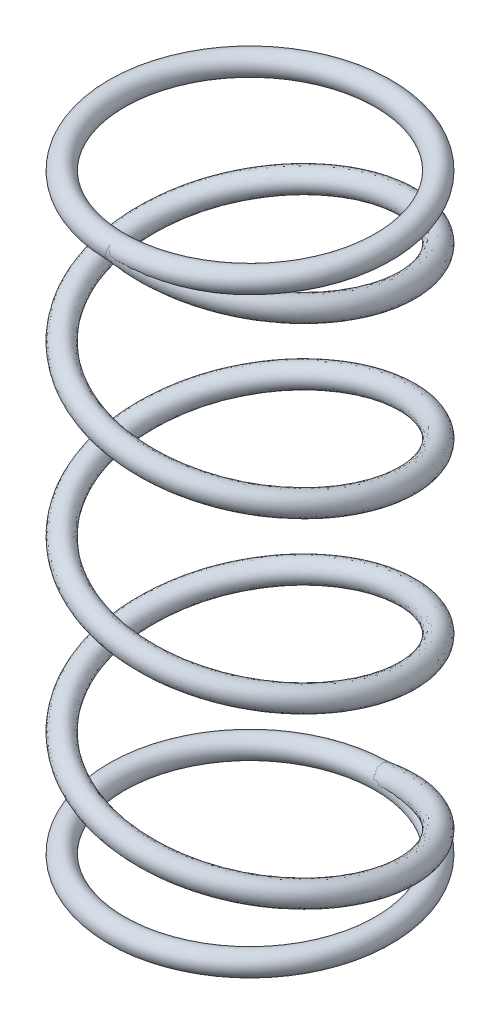
SolidWorks part; units mm, degrees
ref_plane "Front Plane" through (0, 0, 0) normal (0, 0, 1) x (1, 0, 0)
ref_plane "Top Plane" through (0, 0, 0) normal (0, 1, 0) x (1, 0, 0)
ref_plane "Right Plane" through (0, 0, 0) normal (1, 0, 0) x (0, 0, -1)
sketch "Sketch3" plane through (0, 0, 0) normal (0, 1, 0) x (1, 0, 0)
  circle A0 centre (0, 0) radius 4.5
  dimension "D1" = 9
curve "Helix/Spiral1" pitch 5.7143 height 20 turns 3.5
ref_plane "Plane2" through (0, 0, -4.5) normal (0.9802, 0.1981, 0) x (0, 0, -1)
sketch "Sketch7" plane through (0, 0, -4.5) normal (0.9802, 0.1981, 0) x (0, 0, -1)
  circle A0 centre (0, 0) radius 0.375
  spline S0 degree 3 poles (0, 0) (0, 0.0014) (-0.0027, 0) (-0.0055, 0) (-0.007, 0) (-0.0112, 0.0001) (-0.014, 0.0001) (-0.0224, 0.0001) (-0.028, 0.0002) (-0.0448, 0.0004) (-0.056, 0.0006) (-0.0896, 0.0012) (-0.112, 0.0016) (-0.1791, 0.0033) (-0.2239, 0.0046) (-0.3582, 0.0093) (-0.4477, 0.0132) (-0.7161, 0.0266) (-0.895, 0.0378) (-1.4311, 0.0769) (-1.788, 0.1102) (-2.8565, 0.2285) (-3.5663, 0.332) (-4.975, 0.5971) (-5.6748, 0.7576) (-6.7024, 1.0737) (-7.0412, 1.1918) (-7.7017, 1.47) (-8.0254, 1.629) (-8.4673, 1.9351) (-8.6075, 2.0488) (-8.8461, 2.3162) (-8.9454, 2.473) (-9.0024, 2.7356) (-9.0051, 2.8267) (-8.9761, 3.0036) (-8.9452, 3.0889) (-8.8205, 3.327) (-8.6976, 3.4619) (-8.428, 3.6981) (-8.2799, 3.8002) (-7.9732, 3.9857) (-7.8142, 4.0687) (-7.328, 4.2981) (-6.9924, 4.4255) (-5.9725, 4.7658) (-5.2748, 4.9363) (-3.8696, 5.2193) (-3.1609, 5.3299) (-1.7378, 5.5022) (-1.0233, 5.5668) (-0.2176, 5.5968) (-0.128, 5.5995) (-0.0272, 5.6008) (-0.016, 5.601) (-0.0034, 5.601) (-0.0021, 5.601) (0.0007, 5.601) (-0.0022, 5.6011) (-0.0064, 5.6011) (-0.0092, 5.6011) (-0.0176, 5.6011) (-0.0231, 5.6012) (-0.0511, 5.6015) (-0.0735, 5.6019) (-0.1407, 5.6033) (-0.1855, 5.6045) (-0.4094, 5.6117) (-0.5883, 5.6206) (-1.1249, 5.6531) (-1.4821, 5.6826) (-2.5518, 5.79) (-3.2625, 5.8865) (-4.6743, 6.1347) (-5.3759, 6.286) (-6.4099, 6.5804) (-6.7515, 6.6901) (-7.4212, 6.9454) (-7.7505, 7.09) (-8.2154, 7.3599) (-8.3655, 7.4588) (-8.6427, 7.686) (-8.771, 7.8149) (-8.9127, 8.0432) (-8.9509, 8.1253) (-8.9977, 8.2983) (-9.0056, 8.3891) (-8.9763, 8.6563) (-8.8888, 8.8213) (-8.6642, 9.1006) (-8.5274, 9.2189) (-8.2379, 9.4301) (-8.0842, 9.5231) (-7.611, 9.778) (-7.2793, 9.9164) (-6.269, 10.2841) (-5.5736, 10.4653) (-4.1723, 10.7671) (-3.4647, 10.8851) (-2.0435, 11.0721) (-1.3297, 11.1421) (-0.435, 11.19) (-0.256, 11.1979) (-0.0545, 11.2015) (-0.0321, 11.2019) (-0.0069, 11.2021) (-0.0041, 11.2021) (0.0015, 11.2021) (-0.0043, 11.2021) (-0.0127, 11.2022) (-0.0183, 11.2022) (-0.0351, 11.2024) (-0.0463, 11.2025) (-0.1023, 11.2034) (-0.1471, 11.2045) (-0.2814, 11.2084) (-0.3709, 11.2119) (-0.8184, 11.2326) (-1.176, 11.2583) (-2.2467, 11.3545) (-2.9583, 11.444) (-4.3728, 11.6763) (-5.0762, 11.8187) (-6.1155, 12.0936) (-6.4592, 12.1958) (-7.1361, 12.4315) (-7.4699, 12.5641) (-7.9502, 12.8057) (-8.1068, 12.8934) (-8.4059, 13.0908) (-8.5491, 13.2003) (-8.7996, 13.4566) (-8.9084, 13.6055) (-8.9909, 13.8613) (-9.0039, 13.9514) (-8.994, 14.1304) (-8.9716, 14.2185) (-8.8665, 14.4659) (-8.75, 14.6075) (-8.4893, 14.8533) (-8.3435, 14.9591) (-7.8888, 15.2459) (-7.5622, 15.3974) (-6.8968, 15.6637) (-6.5565, 15.7775) (-5.8693, 15.9807) (-5.522, 16.07) (-4.4744, 16.3113) (-3.7681, 16.4371) (-2.3489, 16.6389) (-1.6357, 16.7152) (-0.7418, 16.7749) (-0.5629, 16.785) (-0.2944, 16.7963) (-0.2048, 16.7994) (-0.0929, 16.8019) (-0.0705, 16.8023) (-0.0369, 16.8028) (-0.0257, 16.803) (-0.0117, 16.8031) (-0.0089, 16.8031) (-0.0047, 16.8031) (-0.0033, 16.8031) (-0.0005, 16.8031) (-0.0009, 16.8031) (-0.0079, 16.8032) (-0.0135, 16.8032) (-0.0639, 16.8037) (-0.1087, 16.8046) (-0.5117, 16.8151) (-0.8695, 16.8375) (-1.9413, 16.9218) (-2.6537, 17.0047) (-4.0707, 17.2215) (-4.7755, 17.3554) (-5.8193, 17.6128) (-6.165, 17.7082) (-6.8476, 17.9268) (-7.1849, 18.0494) (-7.6761, 18.2678) (-7.8372, 18.3466) (-8.1501, 18.5213) (-8.3022, 18.6171) (-8.5859, 18.836) (-8.7187, 18.9595) (-8.9266, 19.2513) (-9, 19.4222) (-9, 19.6037) knots 0 0 0 0 0.000004 0.000004 0.000008 0.000008 0.000017 0.000017 0.000034 0.000034 0.000067 0.000067 0.000134 0.000134 0.000269 0.000269 0.000538 0.000538 0.001075 0.001075 0.00215 0.00215 0.0043 0.0043 0.006451 0.006451 0.007526 0.007526 0.008601 0.008601 0.009138 0.009138 0.009676 0.009676 0.009945 0.009945 0.010213 0.010213 0.010751 0.010751 0.011288 0.011288 0.011826 0.011826 0.012901 0.012901 0.015051 0.015051 0.017201 0.017201 0.019352 0.019352 0.01962 0.01962 0.019654 0.019654 0.019658 0.019658 0.019662 0.019662 0.019671 0.019671 0.019688 0.019688 0.019755 0.019755 0.019889 0.019889 0.020427 0.020427 0.021502 0.021502 0.023652 0.023652 0.025802 0.025802 0.026877 0.026877 0.027952 0.027952 0.02849 0.02849 0.029027 0.029027 0.029296 0.029296 0.029565 0.029565 0.030102 0.030102 0.03064 0.03064 0.031178 0.031178 0.032253 0.032253 0.034403 0.034403 0.036553 0.036553 0.038703 0.038703 0.039241 0.039241 0.039308 0.039308 0.039316 0.039316 0.039325 0.039325 0.039341 0.039341 0.039375 0.039375 0.039509 0.039509 0.039778 0.039778 0.040853 0.040853 0.043003 0.043003 0.045154 0.045154 0.046229 0.046229 0.047304 0.047304 0.047841 0.047841 0.048379 0.048379 0.048916 0.048916 0.049185 0.049185 0.049454 0.049454 0.049992 0.049992 0.050529 0.050529 0.051604 0.051604 0.052679 0.052679 0.053754 0.053754 0.055904 0.055904 0.058055 0.058055 0.058592 0.058592 0.058861 0.058861 0.058928 0.058928 0.058962 0.058962 0.05897 0.05897 0.058974 0.058974 0.058979 0.058979 0.058995 0.058995 0.05913 0.05913 0.060205 0.060205 0.062355 0.062355 0.064505 0.064505 0.06558 0.06558 0.066655 0.066655 0.067193 0.067193 0.06773 0.06773 0.068268 0.068268 0.068806 0.068806 0.068806 0.068806 construction
  point P3 (0, 0)
  dimension "D1" = 0.75
sweep "Sweep1" add profiles "Sketch7" path "Helix/Spiral1"
ref_plane "Plane5" through (0, 0, 0) normal (0, 1, 0) x (1, 0, 0)
sketch "Sketch25" plane through (0, 0, 0) normal (0, 1, 0) x (1, 0, 0)
  circle A0 centre (0, 0) radius 4.5
  point P3 (-4.5, 0)
  dimension "D1" = 9
ref_plane "Plane6" through (0, 0, 0) normal (0, 0, 1) x (1, 0, 0)
sketch "Sketch26" plane through (0, 0, 0) normal (0, 0, 1) x (1, 0, 0)
  circle A0 centre (-4.5, 0) radius 0.375
  dimension "D1" = 0.75
sweep "Sweep16" add profiles "Sketch26" path "Sketch25"
ref_plane "Plane7" through (0, 20, 0) normal (0, 1, 0) x (1, 0, 0)
sketch "Sketch27" plane through (0, 20, 0) normal (0, 1, 0) x (1, 0, 0)
  circle A0 centre (0, 0) radius 4.5
  ellipse E0 centre (0, -4.5) end of major axis (0, -4.875) minor radius 0.0743 construction
  point P15 (0, -4.5)
sketch "Sketch28" plane through (0, 0, 0) normal (0, 0, 1) x (1, 0, 0)
  line L0 (4.5, 20) -> (-4.5, 20) construction
  circle A0 centre (-4.5, 20) radius 0.375
  point P0 (-4.5, 20)
  dimension "D1" = 0.75
sweep "Sweep18" add profiles "Sketch28" path "Sketch27"
